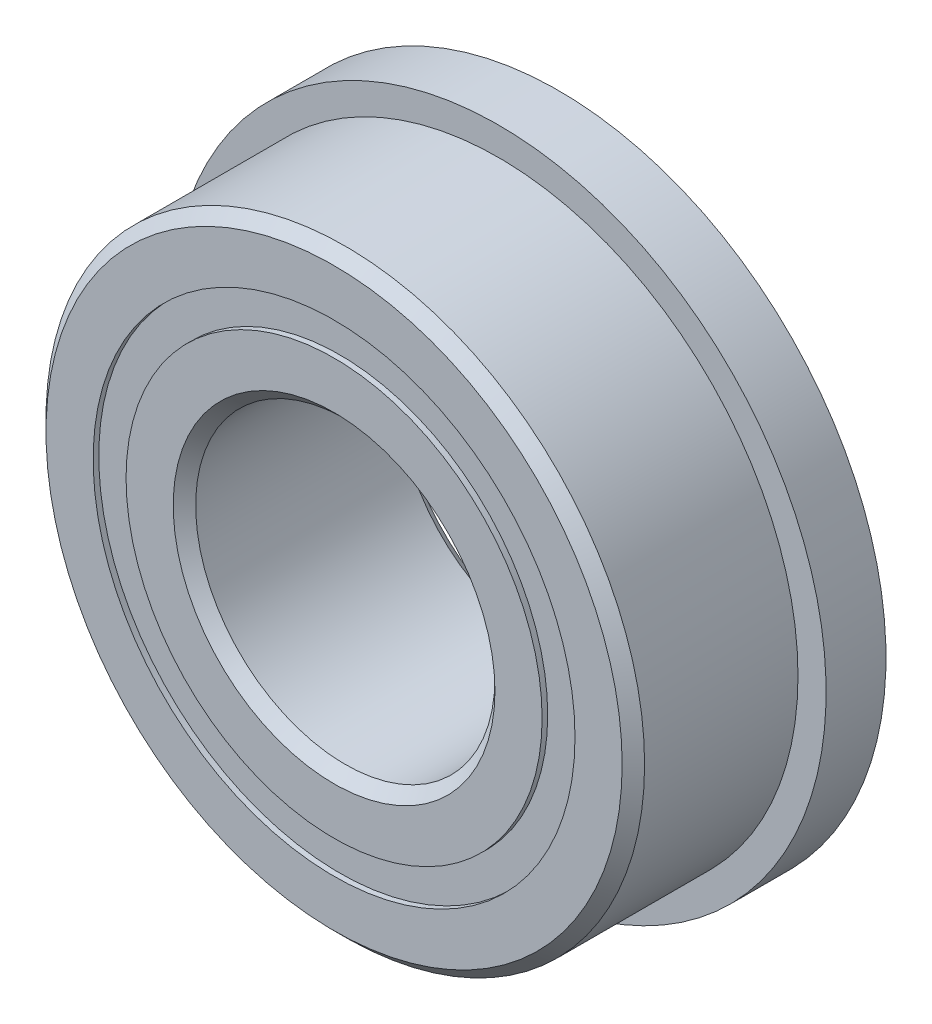
SolidWorks part; units mm, degrees
note: '?' marks a value the reader was unsure of.
ref_plane "Front Plane" through (0, 0, 0) normal (0, 0, 1) x (1, 0, 0)
ref_plane "Top Plane" through (0, 0, 0) normal (0, 1, 0) x (1, 0, 0)
ref_plane "Right Plane" through (0, 0, 0) normal (1, 0, 0) x (0, 0, -1)
sketch "Sketch1" plane through (0, 0, 0) normal (1, 0, 0) x (0, 0, -1)
  line L0 (-2.3813, 0) -> (2.3813, 0) construction
  line L1 (0, 6.35) -> (0, -6.35) construction
  line L2 (2.1431, 6.35) -> (-2.1431, 6.35)
  line L3 (-2.1431, 6.35) -> (-2.3813, 6.1119)
  line L4 (-2.3813, 6.1119) -> (-2.3813, 5.1114)
  line L5 (-2.3813, 5.1114) -> (-1.0583, 5.1114)
  line L6 (2.3813, 5.1114) -> (1.0583, 5.1114)
  line L7 (2.3813, 6.1119) -> (2.3813, 5.1114)
  line L8 (2.1431, 6.35) -> (2.3813, 6.1119)
  line L9 (0, 6.35) -> (0, 4.7625) construction
  line L10 (0, 4.7625) -> (0, 3.175) construction
  arc A0 (-1.0583, 5.1114) -> (1.0583, 5.1114) centre (0, 4.7625) cw
  point P14 (0, 3.175)
  dimension "Width" = 4.7625
  dimension "OD" = 12.7
  dimension "D1" = 45
  dimension "D2" = 0.2381
  dimension "Shaft Dia" = 6.35
  dimension "D3" = 2.1167
  dimension "D4" = 0.3489
revolve "Revolve1" add sketch "Sketch1" angle 360 about L0
sketch "Sketch3" plane through (0, 0, 0) normal (1, 0, 0) x (0, 0, -1)
  line L0 (-2.3813, 4.4136) -> (-1.0583, 4.4136)
  line L1 (0, 6.35) -> (0, -6.35) construction
  line L2 (-2.3813, 6.1119) -> (-2.3813, 5.1114) construction
  line L3 (-2.3813, 4.4136) -> (-2.3813, 3.4131)
  line L4 (-2.1431, 6.35) -> (-2.3813, 6.1119) construction
  line L5 (-2.3813, 3.4131) -> (-2.1431, 3.175)
  line L6 (-2.1431, 3.175) -> (2.1431, 3.175)
  line L7 (2.1431, 6.35) -> (2.1431, -6.35) construction
  line L8 (2.1431, 3.175) -> (2.3813, 3.4131)
  line L9 (2.3813, -6.1119) -> (2.3813, 6.1119) construction
  line L10 (2.3813, 3.4131) -> (2.3813, 4.4136)
  line L11 (2.3813, 4.4136) -> (1.0583, 4.4136)
  line L13 (2.1431, 6.35) -> (2.3813, 6.1119) construction
  arc A0 (1.0583, 5.1114) -> (-1.0583, 5.1114) centre (0, 4.7625) ccw construction
  arc A1 (1.0583, 4.4136) -> (-1.0583, 4.4136) centre (0, 4.7625) cw
revolve "Revolve3" add sketch "Sketch3" angle 360 about L0
sketch "Sketch4" plane through (0, 0, 0) normal (1, 0, 0) x (0, 0, -1)
  line L0 (-1.1144, 4.7625) -> (1.1144, 4.7625)
  arc A2 (-1.1144, 4.7625) -> (1.1144, 4.7625) centre (0, 4.7625) cw
  arc A3 (1.0583, 5.1114) -> (-1.0583, 5.1114) centre (0, 4.7625) ccw construction
revolve "Revolve4" add sketch "Sketch4" angle 360 about L0
ref_axis "Axis1" through (0, 0, -2.3813) along (0, 0, 1)?
pattern_circular "CirPattern1" count 12 every 30 about axis through (0, 0, 0) along (0, 0, 1) of bodies 104
sketch "Sketch5" plane through (0, 0, 0) normal (1, 0, 0) x (0, 0, -1)
  line L0 (-2.3813, 5.1114) -> (-1.0583, 5.1114) construction
  line L1 (-2.2622, 5.1114) -> (-1.1144, 5.1114)
  line L2 (-2.2622, 5.1114) -> (-2.2622, 4.4136)
  line L3 (-2.2622, 4.4136) -> (-1.1144, 4.4136)
  line L4 (-1.1144, 5.1114) -> (-1.1144, 4.4136)
  line L5 (-2.3813, 4.4136) -> (-1.0583, 4.4136) construction
  line L6 (2.3813, 5.1114) -> (1.0583, 5.1114) construction
  line L7 (2.2622, 5.1114) -> (1.1144, 5.1114)
  line L8 (2.2622, 5.1114) -> (2.2622, 4.4136)
  line L9 (2.2622, 4.4136) -> (1.1144, 4.4136)
  line L10 (1.1144, 5.1114) -> (1.1144, 4.4136)
  line L11 (2.3813, 4.4136) -> (1.0583, 4.4136) construction
  line L12 (-2.1431, 6.35) -> (-2.3813, 6.1119) construction
  point P18 (-2.2622, 6.2309)
revolve "Revolve5" add sketch "Sketch5" angle 360 about L0
sketch "Sketch6" plane through (0, 0, 0) normal (1, 0, 0) x (0, 0, -1)
  line L0 (2.3813, 0) -> (-2.3813, 0) construction
  line L1 (2.3813, 5.1114) -> (1.1113, 5.1114)
  line L2 (2.3813, 5.1114) -> (2.3813, 6.9469)
  line L3 (2.3813, 6.9469) -> (1.1113, 6.9469)
  line L4 (1.1113, 5.1114) -> (1.1113, 6.9469)
  dimension "Th" = 1.27
  dimension "Flange OD" = 13.8938
revolve "Revolve6" add sketch "Sketch6" angle 360 about L0
equation "\"D2@Sketch1\" = \"Width@Sketch1\"*.05"
equation "\"D3@Sketch1\" = \"Width@Sketch1\"/2.25"
equation "\"D4@Sketch1\" = (((\"OD@Sketch1\"-\"Width@Sketch1\")/2)/3.25)/3.5"
equation "\"D2@CirPattern1\" = 360/\"Balls@CirPattern1\""
